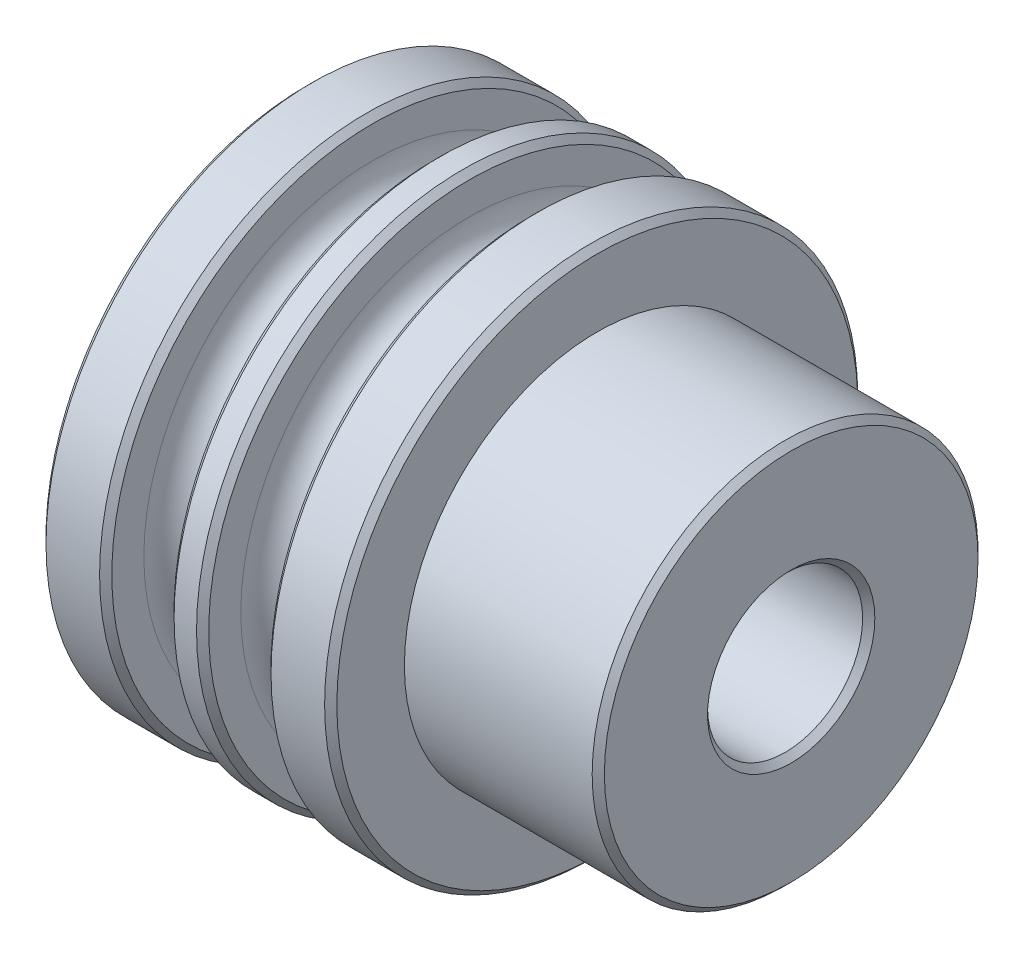
SolidWorks part; units mm, degrees
material "Nylon 101"
ref_plane "Front Plane" through (0, 0, 0) normal (0, 0, 1) x (1, 0, 0)
ref_plane "Top Plane" through (0, 0, 0) normal (0, 1, 0) x (1, 0, 0)
ref_plane "Right Plane" through (0, 0, 0) normal (1, 0, 0) x (0, 0, -1)
sketch "Sketch1" plane through (0, 0, 0) normal (1, 0, 0) x (0, 0, -1)
  circle A0 centre (0, 0) radius 12.6365
  dimension "D1" = 25.273
extrude "Boss-Extrude1" add sketch "Sketch1" along normal blind 12.7
sketch "Sketch2" plane through (0, 0, 0) normal (-1, 0, 0) x (0, 0, 1)
  circle A0 centre (0, 0) radius 17.4625
  dimension "D1" = 34.925
extrude "Boss-Extrude2" add sketch "Sketch2" along normal blind 19.05
sketch "Sketch3" plane through (-19.05, 0, 0) normal (-1, 0, 0) x (0, 0, 1)
  circle A0 centre (0, 0) radius 11.1125
  dimension "D1" = 22.225
extrude "Cut-Extrude1" cut sketch "Sketch3" against normal blind 7.112
sketch "Sketch4" plane through (-11.938, 0, 0) normal (-1, 0, 0) x (0, 0, 1)
  circle A0 centre (0, 0) radius 7.2746
  dimension "D1" = 14.5492
extrude "Cut-Extrude2" cut sketch "Sketch4" against normal blind 0.2
sketch "Sketch5" plane through (-11.738, 0, 0) normal (-1, 0, 0) x (0, 0, 1)
  circle A0 centre (0, 0) radius 5.08
  dimension "D1" = 10.16
extrude "Cut-Extrude3" cut sketch "Sketch5" against normal through all
sketch "Sketch6" plane through (0, 0, 0) normal (0, 0, 1) x (1, 0, 0)
  line L0 (-8.39, 17.4625) -> (-8.39, 14.9625)
  line L1 (0, 17.4625) -> (-19.05, 17.4625) construction
  line L2 (-4.31, 17.4625) -> (-4.31, 14.9625)
  line L3 (-6.35, 12.9225) -> (-6.35, 0) construction
  line L4 (-6.35, 14.9625) -> (-6.35, 17.4625) construction
  line L5 (-8.39, 17.4625) -> (-4.31, 17.4625)
  line L6 (-8.39, 17.4625) -> (-4.31, 17.4625)
  line L7 (-6.35, 0) -> (0, 0) construction
  line L8 (0, -17.4625) -> (0, 17.4625) construction
  arc A0 (-8.39, 14.9625) -> (-4.31, 14.9625) centre (-6.35, 14.9625) ccw
  dimension "D1" = 2.04
  dimension "D2" = 12.9225
  dimension "D3" = 2.5
  dimension "D4" = 6.35
revolve "Cut-Revolve1" cut sketch "Sketch6" angle 360 about L7 region at (-6.35, 15.3861, 0)
pattern_linear "LPattern1" count 2 spacing 6.35 along (-1, 0, 0) of "Cut-Revolve1"
chamfer "Chamfer1" distance 0.4 angle 45 9 edges at (12.7, 0, -12.6365) (12.7, 0, 5.08) (-19.05, 0, 17.4625) (-19.05, 0, 11.1125) (-14.74, 0, 17.4625) (-8.39, 0, 17.4625) (-10.66, 0, 17.4625) (0, 0, 17.4625) (-4.31, 0, 17.4625)
equation "\"D1@Sketch6\"=2mm+.04mm"
equation "\"D2@Sketch6\"=19mm/2"
equation "\"D3@Sketch6\"=2.5mm"
